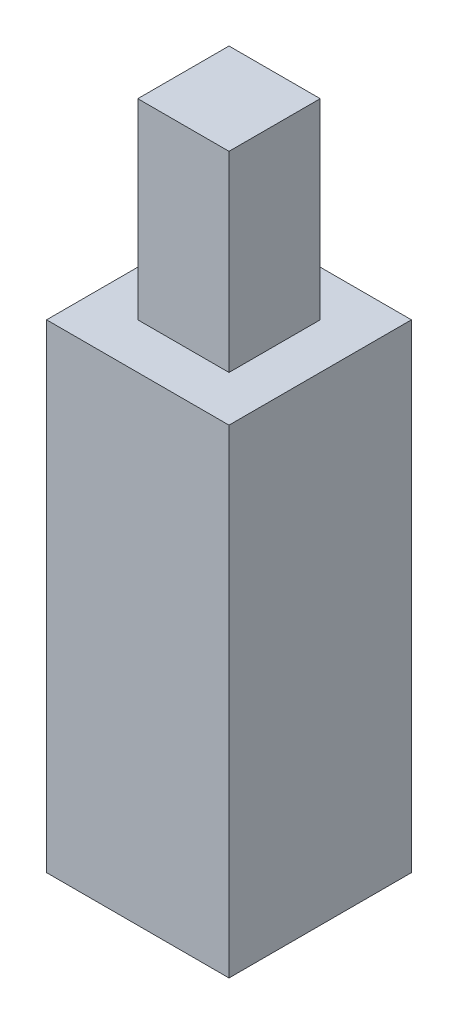
SolidWorks part; units mm, degrees
ref_plane "Front Plane" through (0, 0, 0) normal (0, 0, 1) x (1, 0, 0)
ref_plane "Top Plane" through (0, 0, 0) normal (0, 1, 0) x (1, 0, 0)
ref_plane "Right Plane" through (0, 0, 0) normal (1, 0, 0) x (0, 0, -1)
sketch "Sketch1" plane through (0, 0, 0) normal (0, 1, 0) x (1, 0, 0)
  line L1 (0, 0) -> (7.62, 0)
  line L2 (0, 0) -> (0, 7.62)
  line L3 (0, 7.62) -> (7.62, 7.62)
  line L4 (7.62, 0) -> (7.62, 7.62)
  dimension "D1" = 7.62
  dimension "D2" = 7.62
extrude "Boss-Extrude1" add sketch "Sketch1" along normal blind 20
sketch "Sketch2" plane through (0, 20, 0) normal (0, 1, 0) x (1, 0, 0)
  line L6 (0, 7.62) -> (0, 0) construction
  line L7 (5.715, 1.905) -> (1.905, 1.905)
  line L8 (5.715, 1.905) -> (5.715, 5.715)
  line L9 (5.715, 5.715) -> (1.905, 5.715)
  line L10 (1.905, 1.905) -> (1.905, 5.715)
  line L11 (5.715, 1.905) -> (1.905, 5.715) construction
  line L12 (5.715, 5.715) -> (1.905, 1.905) construction
  line L13 (0, 0) -> (7.62, 0) construction
  point P0 (3.81, 3.81)
  dimension "D1" = 3.81
  dimension "D2" = 3.81
  dimension "D3" = 3.81
  dimension "D4" = 3.81
extrude "Boss-Extrude2" add sketch "Sketch2" along normal blind 8
sketch "Sketch3" plane through (0, 0, 0) normal (0, -1, 0) x (-1, 0, 0)
  line L0 (0, 0) -> (-7.62, 0) construction
  line L1 (-6.985, 6.985) -> (-0.635, 6.985)
  line L2 (-6.985, 6.985) -> (-6.985, 0.635)
  line L3 (-6.985, 0.635) -> (-0.635, 0.635)
  line L4 (-0.635, 6.985) -> (-0.635, 0.635)
  line L5 (-6.985, 6.985) -> (-0.635, 0.635) construction
  line L6 (-6.985, 0.635) -> (-0.635, 6.985) construction
  line L7 (0, 7.62) -> (0, 0) construction
  point P0 (-3.81, 3.81)
  dimension "D1" = 3.81
  dimension "D2" = 3.81
  dimension "D3" = 6.35
  dimension "D4" = 6.35
extrude "Cut-Extrude1" cut sketch "Sketch3" against normal blind 1.016
